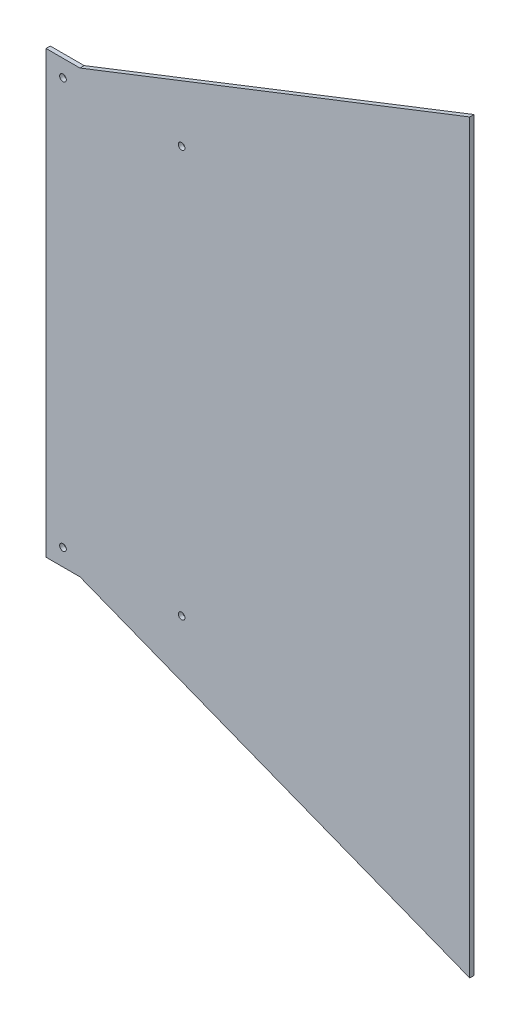
SolidWorks part; units mm, degrees
ref_plane "Front Plane" through (0, 0, 0) normal (1, 0, 0) x (0, 1, 0)
ref_plane "Top Plane" through (0, 0, 0) normal (0, 0, 1) x (0, 1, 0)
ref_plane "Right Plane" through (0, 0, 0) normal (0, 1, 0) x (-1, 0, 0)
sketch "Sketch1" plane through (0, 0, 0) normal (0, 0, 1) x (0, 1, 0)
  line L0 (-330.2, -25.4) -> (-330.2, 0)
  line L1 (-330.2, 0) -> (0, 0)
  line L2 (0, 0) -> (0, -25.4)
  line L3 (-330.2, -25.4) -> (-444.5, -317.5)
  line L4 (-444.5, -317.5) -> (114.3, -317.5)
  line L5 (114.3, -317.5) -> (0, -25.4)
  point P2 (-165.1, -317.5)
  point P7 (-165.1, 0)
  dimension "D1" = 330.2
  dimension "D2" = 25.4
  dimension "D3" = 558.8
  dimension "D4" = 292.1
extrude "Boss-Extrude1" add sketch "Sketch1" along normal blind 3.175
sketch "Sketch2" plane through (0, 0, 0) normal (0, 0, -1) x (1, 0, 0)
  line L0 (0, 0) -> (0, 330.2) construction
  line L1 (0, 330.2) -> (25.4, 330.2) construction
  line L2 (25.4, 0) -> (0, 0) construction
  point P0 (12.7, 317.5)
  point P1 (12.7, 12.7)
  point P15 (101.6, 317.5)
  point P17 (101.6, 12.7)
  dimension "D1" = 12.7
  dimension "D2" = 12.7
  dimension "D3" = 12.7
  dimension "D4" = 88.9
hole_wizard "#9 (0.196) Diameter Hole1" positions "Sketch2" profile "Sketch3" hole size "#9" standard "ANSI Inch" end condition through all
sketch "Sketch3" plane through (12.7, -317.5, 0) normal (1, 0, 0) x (0, 1, 0)
  line L0 (0, 0) -> (0, 3.175)
  line L1 (0, 3.175) -> (2.4892, 3.175)
  line L2 (2.4892, 3.175) -> (2.4892, 0)
  line L5 (2.4892, 0) -> (0, 0)
  line L11 (0, -6.35) -> (0, 107.95) construction
  dimension "Thru Hole Dia." = 4.9784
  dimension "Thru Hole Depth" = 3.175
